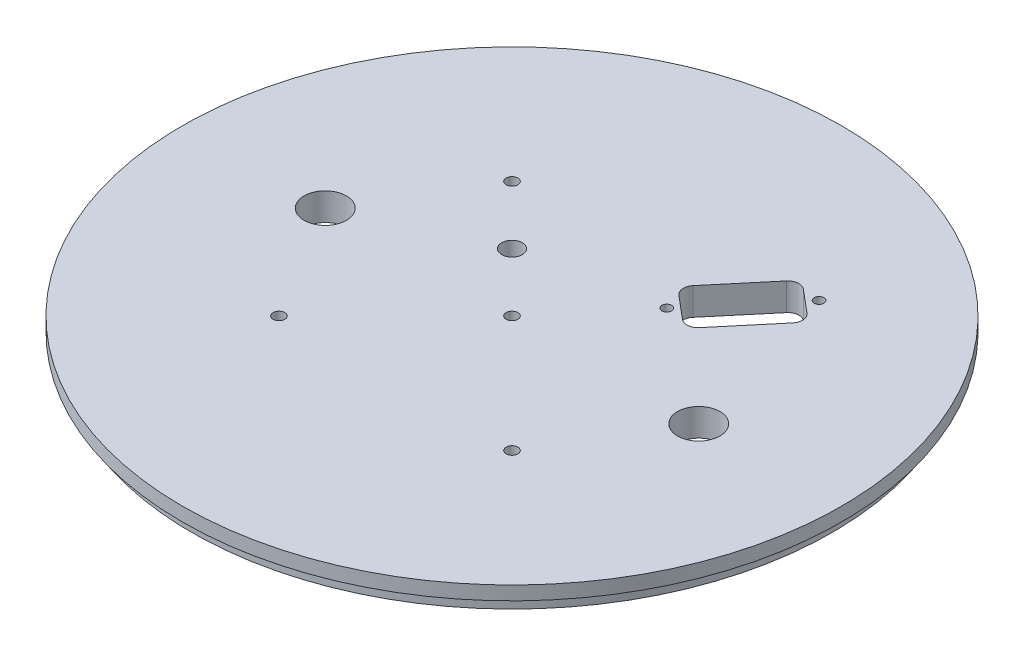
SolidWorks part; units mm, degrees
material "6061-T6 (SS)"
ref_plane "Front Plane" through (0, 0, 0) normal (0, 0, 1) x (1, 0, 0)
ref_plane "Top Plane" through (0, 0, 0) normal (0, 1, 0) x (1, 0, 0)
ref_plane "Right Plane" through (0, 0, 0) normal (1, 0, 0) x (0, 0, -1)
sketch "Sketch1" plane through (0, 0, 0) normal (0, 1, 0) x (1, 0, 0)
  line L0 (0, -76.2) -> (0, 76.2) construction
  line L1 (-76.2, 0) -> (76.2, 0) construction
  line L2 (-26.9408, 26.9408) -> (0, 0) construction
  line L3 (0, 56.7387) -> (0, 29.6936) construction
  line L4 (3.6407, 56.7387) -> (3.6407, 29.6936) construction
  line L5 (-3.6407, 56.7387) -> (-3.6407, 29.6936) construction
  line L6 (0, -56.7387) -> (0, -29.6936) construction
  line L7 (3.6407, -56.7387) -> (3.6407, -29.6936) construction
  line L8 (-3.6407, -56.7387) -> (-3.6407, -29.6936) construction
  line L9 (-53.8815, -53.8815) -> (54.3236, 54.3236) construction
  line L10 (-26.9408, -26.9408) -> (0, 0) construction
  circle A0 centre (0, 0) radius 76.2
  circle A1 centre (0, 0) radius 3.175 construction
  circle A2 centre (43.18, 0) radius 4.9022
  circle A3 centre (-43.18, 0) radius 4.9022
  circle A4 centre (-26.9408, 26.9408) radius 1.3589
  arc A6 (3.6407, 56.7387) -> (-3.6407, 56.7387) centre (0, 56.7387) ccw construction
  arc A7 (-3.6407, 29.6936) -> (3.6407, 29.6936) centre (0, 29.6936) ccw construction
  arc A8 (3.6407, -56.7387) -> (-3.6407, -56.7387) centre (0, -56.7387) cw construction
  arc A9 (-3.6407, -29.6936) -> (3.6407, -29.6936) centre (0, -29.6936) cw construction
  circle A10 centre (26.9408, -26.9408) radius 1.3589
  circle A11 centre (-13.4704, 13.4704) radius 2.3813
  circle A13 centre (-26.9408, -26.9408) radius 1.3589
  circle A14 centre (0, 0) radius 38.1 construction
  circle A15 centre (0, 0) radius 1.3589
  point P16 (0, 43.2162)
  point P19 (0, 0)
  point P26 (0, -43.2162)
  dimension "D1" = 152.4
  dimension "D2" = 6.35
  dimension "D3" = 9.8044
  dimension "D5" = 2.7178
  dimension "D8" = 4.7625
  dimension "D10" = 2.7178
  dimension "D12" = 2.7178
  dimension "D6" = 38.1
  dimension "D7" = 45
  dimension "D4" = 45
  dimension "D9" = 43.18
  dimension "D11" = 38.1
extrude "Boss-Extrude1" add sketch "Sketch1" along normal blind 6.35
sketch "Sketch2" plane through (0, 0, 0) normal (0, -1, 0) x (1, 0, 0)
  circle A0 centre (0, 0) radius 76.2
  circle A1 centre (0, 0) radius 74.041
  dimension "D1" = 152.4
  dimension "D2" = 148.082
extrude "Cut-Extrude1" cut sketch "Sketch2" against normal blind 3.175
sketch "Sketch3" plane through (0, 6.35, 0) normal (0, 1, 0) x (1, 0, 0)
  line L0 (0, 76.2) -> (0, -76.2) construction
  line L1 (-76.2, 0) -> (76.2, 0) construction
  line L2 (0, 34.798) -> (0, 13.97) construction
  line L3 (3.2385, 34.798) -> (3.2385, 13.97)
  line L4 (-3.2385, 34.798) -> (-3.2385, 13.97)
  line L5 (0, -34.798) -> (0, -13.97) construction
  line L6 (3.2385, -34.798) -> (3.2385, -13.97)
  line L7 (-3.2385, -34.798) -> (-3.2385, -13.97)
  circle A0 centre (0, 0) radius 76.2 construction
  arc A1 (3.2385, 34.798) -> (-3.2385, 34.798) centre (0, 34.798) ccw
  arc A2 (-3.2385, 13.97) -> (3.2385, 13.97) centre (0, 13.97) ccw
  arc A3 (3.2385, -34.798) -> (-3.2385, -34.798) centre (0, -34.798) cw
  arc A4 (-3.2385, -13.97) -> (3.2385, -13.97) centre (0, -13.97) cw
  point P7 (0, 13.97)
  point P8 (0, 34.798)
  point P12 (0, 24.384)
  point P20 (0, -24.384)
  point P25 (0, -34.798)
  point P26 (0, -13.97)
  dimension "D1" = 13.97
  dimension "D2" = 20.828
  dimension "D3" = 6.477
extrude "Cut-Extrude2" cut sketch "Sketch3" against normal blind 3.556 from offset 3.175 offset against normal yes
hole_wizard "Tap Drill for #4-40 Tap1" positions "Sketch5" profile "Sketch6" hole size "#4-40" standard "ANSI Inch" end condition through all
sketch "Sketch5" plane through (0, 6.35, 0) normal (0, 1, 0) x (1, 0, 0)
  line L0 (0, 0) -> (53.6567, 63.9455) construction
  line L2 (0, 0) -> (43.18, 0) construction
  point P0 (16.3268, 19.4575)
  point P2 (32.3965, 38.6086)
  dimension "D1" = 50
  dimension "D2" = 25
  dimension "D3" = 25.4
sketch "Sketch6" plane through (16.3268, 6.35, -19.4575) normal (1, 0, 0) x (0, 0, 1)
  line L0 (0, 0) -> (0, 6.35)
  line L1 (0, 6.35) -> (1.1303, 6.35)
  line L2 (1.1303, 6.35) -> (1.1303, 0)
  line L5 (1.1303, 0) -> (0, 0)
  line L11 (0, -6.35) -> (0, 107.95) construction
  dimension "Thru Hole Dia." = 2.2606
  dimension "Thru Hole Depth" = 6.35
sketch "Sketch4" plane through (0, 6.35, 0) normal (0, 1, 0) x (1, 0, 0)
  line L0 (15.1695, 23.4128) -> (20.423, 19.0046)
  line L1 (14.8564, 26.9913) -> (24.7219, 38.7485)
  line L2 (24.0014, 19.3177) -> (33.8669, 31.0749)
  line L3 (28.3003, 39.0616) -> (33.5538, 34.6533)
  line L4 (0, 0) -> (32.3965, 38.6086) construction
  circle A1 centre (16.3268, 19.4575) radius 1.1303 construction
  arc A2 (24.7219, 38.7485) -> (28.3003, 39.0616) centre (26.6676, 37.1158) cw
  arc A3 (33.8669, 31.0749) -> (33.5538, 34.6533) centre (31.9212, 32.7076) ccw
  arc A4 (20.423, 19.0046) -> (24.0014, 19.3177) centre (22.0557, 20.9503) ccw
  arc A5 (14.8564, 26.9913) -> (15.1695, 23.4128) centre (16.8021, 25.3586) ccw
  point P11 (17.7962, 21.2087)
  dimension "D4" = 2.54
  dimension "D1" = 2.286
  dimension "D2" = 2.286
  dimension "D3" = 11.938
extrude "Cut-Extrude3" cut sketch "Sketch4" against normal through all
equation "\"leadDist\"=1.5"
equation "\"Lead_Screw_Dist\" = 3.4in"
equation "\"D9@Sketch1\"=\"Lead_Screw_Dist\"/2"
equation "\"Lead_Screw_Diam\" = 0.386in"
equation "\"D3@Sketch1\"=\"Lead_Screw_Diam\""
equation "\"Bodytube_OD\" = 6.17in"
equation "\"Bodytube_ID\" = 5.998in"
equation "\"Motor_OD\" = 4in"
equation "\"Fwd_Tube_Length\" = 40in"
equation "\"Mid_Tube_Length\" = 1in"
equation "\"Aft_Section_Length\"= 39in"
equation "\"AB_Coupler_OD_Length\"= 1in"
equation "\"AB_Coupling_Section_Length\"= 0.375in"
equation "\"AB_Coupler_Length\"= \"AB_Coupler_OD_Length\" + \"AB_Coupling_Section_Length\" * 2"
equation "\"Cutout_Angle\" = 80"
equation "\"AB_Paddle_Height\" = 0.375in"
equation "\"AB_Coupler_Num_Screws\"= 4"
equation "\"Num_Cutouts\" = 3"
equation "\"AB_Coupler_OD\"= 6.17in"
equation "\"AB_Coupler_ID\"= 5.75in"
equation "\"AB_Coupler_Surface_Diameter\"= 5.998in"
equation "\"AB_Coupling_Screw_Diameter\"= 0.1065in"
equation "\"AB_Central_Bushing_Length\" = .4724in"
equation "\"Lead_Screw_Length\" = (\"Mid_Coupler_Length\" + 2*0.375in + 2*0.5in)"
equation "\"Paddle_Pin_Offset\" = .25in"
equation "\"Paddle_Pin_Radius\" = 2.25in"
equation "\"SS_Paddle_Pin_Radius\" = 2.25*0.66in"
equation "\"Paddle_Gear_OD\" = 3.2in"
equation "\"Drive_Gear_OD\" = 1.7in"
equation "\"Fwd_BKHD_From_Top\" = 18in"
equation "\"Fin_Thickness\"= .118in"
equation "\"Guiderail_Cutout_Diameter\"= 1.5in"
equation "\"DB9_Hole_Dist\" = 25mm"
equation "\"Airbrakes_Wire_Hole_Dia\" = .25in"
equation "\"Airbrakes_Wire_Hole_Dist\" = 1.1in"
equation "\"Servo_Gear_Offset\" = 0.5in"
equation "\"Mid_Coupler_Length\" = 13in"
equation "\"D2@Sketch5\"=\"DB9_Hole_Dist\""
equation "\"DB9_Relief_Width\" = 0.47in"
equation "\"DB9_Relief_Hole_Offset\" = 0.09in"
equation "\"D1@Sketch4\"=\"DB9_Relief_Hole_Offset\""
equation "\"D2@Sketch4\"=\"DB9_Relief_Hole_Offset\""
equation "\"D3@Sketch4\"=\"DB9_Relief_Width\""
